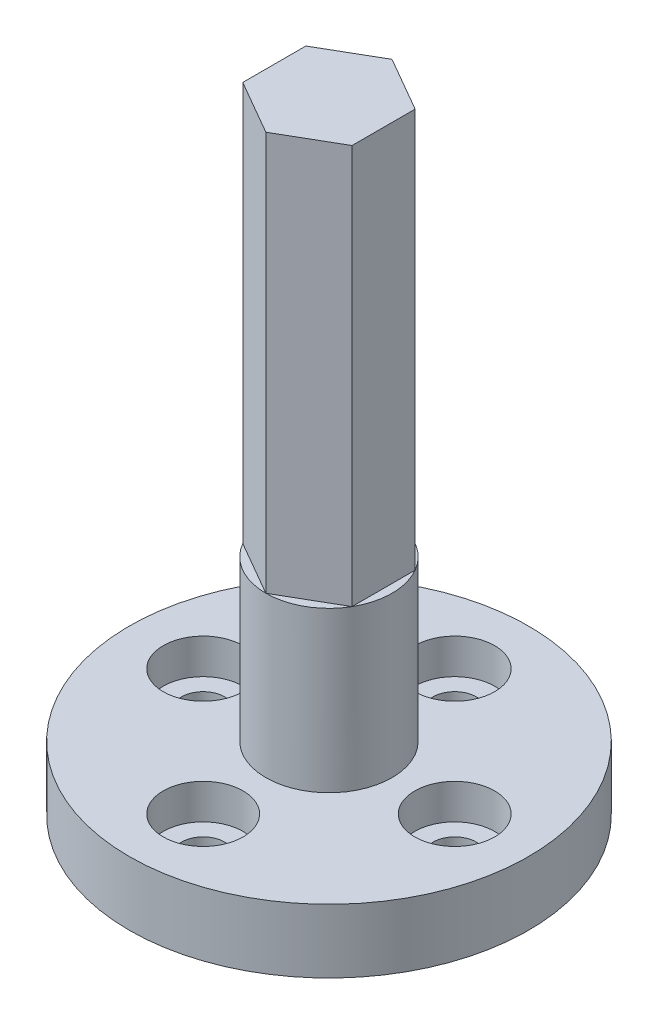
SolidWorks part; units mm, degrees
ref_plane "Alzado" through (0, 0, 0) normal (0, 0, 1) x (1, 0, 0)
ref_plane "Planta" through (0, 0, 0) normal (0, 1, 0) x (1, 0, 0)
ref_plane "Vista lateral" through (0, 0, 0) normal (1, 0, 0) x (0, 0, -1)
sketch "Croquis3" plane through (0, 0, 0) normal (0, 1, 0) x (1, 0, 0)
  circle A0 centre (0, 0) radius 12.5
  dimension "D1" = 25
extrude "Saliente-Extruir1" add sketch "Croquis3" along normal blind 4
sketch "Croquis4" plane through (0, 4, 0) normal (0, 1, 0) x (1, 0, 0)
  circle A0 centre (0, 0) radius 3.95
  dimension "D1" = 7.9
extrude "Saliente-Extruir2" add sketch "Croquis4" along normal blind 35
sketch "Croquis7" plane through (0, 0, 0) normal (0, -1, 0) x (1, 0, 0)
  circle A0 centre (0, 0) radius 12
  dimension "D1" = 24
sketch "Croquis12" plane through (0, 39, 0) normal (0, 1, 0) x (1, 0, 0)
  line L1 (0, 3.95) -> (-3.4208, 1.975)
  line L2 (-3.4208, 1.975) -> (-3.4208, -1.975)
  line L3 (-3.4208, -1.975) -> (0, -3.95)
  line L4 (0, -3.95) -> (3.4208, -1.975)
  line L5 (3.4208, -1.975) -> (3.4208, 1.975)
  line L6 (3.4208, 1.975) -> (0, 3.95)
  circle A0 centre (0, 0) radius 3.95 construction
  circle A1 centre (0, 0) radius 3.95 construction
  circle A2 centre (0, 0) radius 3.95 construction
extrude "Cortar-Extruir7" cut sketch "Croquis12" against normal blind 25 flip side to cut
sketch "Croquis13" plane through (0, 0, 0) normal (0, -1, 0) x (1, 0, 0)
  circle A0 centre (0, 7.875) radius 1.35
  circle A1 centre (7.875, 0) radius 1.35
  circle A2 centre (0, -7.875) radius 1.35
  circle A3 centre (-7.875, 0) radius 1.35
  point P12 (0, 0)
  dimension "D1" = 7.875
  dimension "D3" = 2.7
  dimension "D2" = 4
extrude "Cortar-Extruir8" cut sketch "Croquis13" against normal blind 10
sketch "Croquis14" plane through (0, 4, 0) normal (0, 1, 0) x (1, 0, 0)
  circle A0 centre (0, 7.875) radius 1.35 construction
  circle A1 centre (0, 7.875) radius 1.35 construction
  circle A2 centre (0, 7.875) radius 2.5
  circle A3 centre (7.875, 0) radius 2.5
  circle A4 centre (0, -7.875) radius 2.5
  circle A5 centre (-7.875, 0) radius 2.5
  point P13 (0, 0)
  dimension "D1" = 5
  dimension "D2" = 4
extrude "Cortar-Extruir9" cut sketch "Croquis14" against normal blind 2.2
